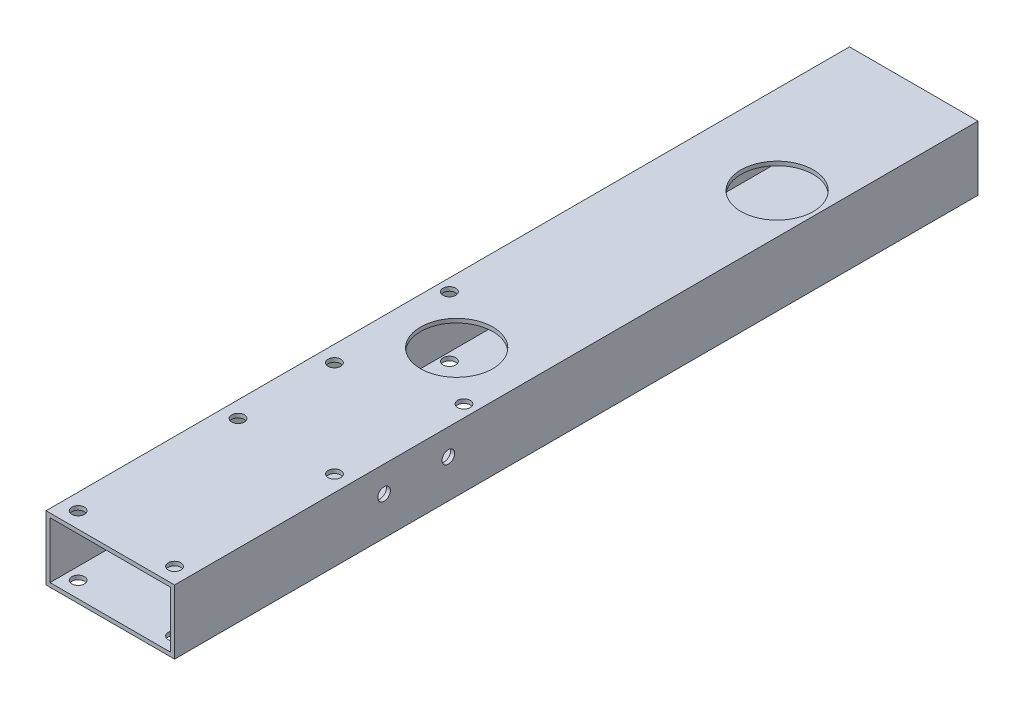
SolidWorks part; units mm, degrees
material "6061 Alloy"
ref_plane "Front Plane" through (0, 0, 0) normal (0, 0, 1) x (1, 0, 0)
ref_plane "Top Plane" through (0, 0, 0) normal (0, 1, 0) x (1, 0, 0)
ref_plane "Right Plane" through (0, 0, 0) normal (1, 0, 0) x (0, 0, -1)
sketch "Sketch1" plane through (0, 0, 0) normal (0, 0, 1) x (1, 0, 0)
  line L0 (-23.8125, 11.1125) -> (23.8125, 11.1125)
  line L2 (-25.4, 12.7) -> (25.4, 12.7)
  line L3 (-25.4, 12.7) -> (-25.4, -12.7)
  line L4 (-25.4, -12.7) -> (25.4, -12.7)
  line L5 (25.4, 12.7) -> (25.4, -12.7)
  line L10 (23.8125, 11.1125) -> (23.8125, -11.1125)
  line L11 (-23.8125, -11.1125) -> (23.8125, -11.1125)
  line L12 (-23.8125, 11.1125) -> (-23.8125, -11.1125)
  point P12 (0, 12.7)
  point P14 (25.4, 0)
  dimension "Wall Thickness" = 1.5875
  dimension "Outside Width" = 50.8
  dimension "Outside Height" = 25.4
  dimension "Inside Height" = 22.225
  dimension "Inside Width" = 47.625
sketch "Sketch2" plane through (0, 0, 0) normal (1, 0, 0) x (0, 0, -1)
  line L0 (158.75, 0) -> (-158.75, 0)
  point P4 (0, 0)
  point P7 (-158.75, 0)
  point P10 (158.75, 0)
  dimension "Length" = 317.5
sketch "Sketch3" plane through (0, 0, 0) normal (0, 0, 1) x (1, 0, 0)
  line L21 (25.4, 12.7) -> (-25.4, 12.7)
  line L22 (25.4, -12.7) -> (25.4, 12.7)
  line L23 (-25.4, -12.7) -> (25.4, -12.7)
  line L24 (-25.4, 12.7) -> (-25.4, -12.7)
  line L25 (25.4, 12.7) -> (-25.4, 12.7)
  line L26 (25.4, -12.7) -> (25.4, 12.7)
  line L27 (-25.4, -12.7) -> (25.4, -12.7)
  line L28 (-25.4, 12.7) -> (-25.4, -12.7)
  line L29 (23.8125, 11.1125) -> (-23.8125, 11.1125)
  line L30 (23.8125, -11.1125) -> (23.8125, 11.1125)
  line L31 (-23.8125, -11.1125) -> (23.8125, -11.1125)
  line L32 (-23.8125, 11.1125) -> (-23.8125, -11.1125)
  line L33 (23.8125, 11.1125) -> (-23.8125, 11.1125)
  line L34 (23.8125, -11.1125) -> (23.8125, 11.1125)
  line L35 (-23.8125, -11.1125) -> (23.8125, -11.1125)
  line L36 (-23.8125, 11.1125) -> (-23.8125, -11.1125)
  dimension "D1" = 0
  dimension "D2" = 0
extrude "Boss-Extrude1" add sketch "Sketch3" along normal up to vertex (158.75 mm away) and the other way up to vertex (158.75 mm away) up to point (0, 0, 158.75) other way up to point (0, 0, -158.75)
sketch "Drawing Reference" plane through (0, 0, 0) normal (1, 0, 0) x (0, 0, -1)
  line L0 (-158.75, 0) -> (158.75, 0) construction
  line L1 (0, -12.7) -> (0, 12.7) construction
  line L2 (-158.75, -12.7) -> (158.75, -12.7) construction
  line L5 (-158.75, 12.7) -> (158.75, 12.7) construction
  point P7 (-122.174, 0)
  point P8 (122.174, 0)
  dimension "D1" = 36.576
sketch "Sketch4" plane through (0, 12.7, 0) normal (0, 1, 0) x (1, 0, 0)
  line L0 (0, 158.75) -> (0, 95.25) construction
  line L1 (25.4, 158.75) -> (-25.4, 158.75) construction
  line L2 (0, 95.25) -> (9.525, 95.25) construction
  line L3 (0, 158.75) -> (0, -26.67) construction
  circle A1 centre (9.525, 95.25) radius 14.2875
  circle A3 centre (9.525, 95.25) radius 117.5004 construction
  circle A4 centre (0, -21.8637) radius 14.2875
  dimension "D1" = 63.5
  dimension "D3" = 235.0008
  dimension "D2" = 9.525
extrude "Cut-Extrude1" cut sketch "Sketch4" against normal blind 39.37
sketch "Sketch6" plane through (0, 12.7, 0) normal (0, 1, 0) x (1, 0, 0)
  line L0 (-20.6308, -4.1018) -> (20.6308, -39.6256) construction
  circle A0 centre (0, -21.8637) radius 27.2234 construction
  point P8 (0, -21.8637)
hole_wizard "#10 Clearance Hole1" positions "Sketch7" profile "Sketch8" hole size "#10" standard "ANSI Inch" end condition through all
sketch "Sketch7" plane through (0, 12.7, 0) normal (0, 1, 0) x (1, 0, 0)
  point P0 (-20.6308, -4.1018)
  point P3 (20.6308, -39.6256)
sketch "Sketch8" plane through (-20.6308, 12.7, 4.1018) normal (1, 0, 0) x (0, 0, 1)
  line L0 (0, 0) -> (0, 25.4)
  line L1 (0, 25.4) -> (2.4892, 25.4)
  line L2 (2.4892, 25.4) -> (2.4892, 0)
  line L5 (2.4892, 0) -> (0, 0)
  line L11 (0, -6.35) -> (0, 107.95) construction
  dimension "Thru Hole Dia." = 4.9784
  dimension "Thru Hole Depth" = 25.4
sketch "Sketch9" plane through (-25.4, 0, 0) normal (-1, 0, 0) x (0, 0, 1)
  line L0 (75.9497, 2.425) -> (50.5497, 2.425) construction
hole_wizard "#10 Clearance Hole2" positions "Sketch12" profile "Sketch13" hole size "#10" standard "ANSI Inch" end condition through all
sketch "Sketch12" plane through (-25.4, 0, 0) normal (-1, 0, 0) x (0, 0, 1)
  point P0 (50.5497, 2.425)
  point P3 (75.9497, 2.425)
sketch "Sketch13" plane through (-25.4, 2.425, 50.5497) normal (0, 1, 0) x (0, 0, 1)
  line L0 (0, 0) -> (0, 50.8)
  line L1 (0, 50.8) -> (2.4892, 50.8)
  line L2 (2.4892, 50.8) -> (2.4892, 0)
  line L5 (2.4892, 0) -> (0, 0)
  line L11 (0, -6.35) -> (0, 107.95) construction
  dimension "Thru Hole Dia." = 4.9784
  dimension "Thru Hole Depth" = 50.8
hole_wizard "#10 Clearance Hole3" positions "Sketch14" profile "Sketch15" hole size "#10" standard "ANSI Inch" end condition through all
sketch "Sketch14" plane through (0, 12.7, 0) normal (0, 1, 0) x (1, 0, 0)
  point P0 (-19.05, -51.1131)
  point P3 (-19.05, -89.2131)
  point P6 (19.05, -89.2131)
  point P9 (19.05, -152.4)
  point P12 (-19.05, -152.4)
sketch "Sketch15" plane through (-19.05, 12.7, 51.1131) normal (1, 0, 0) x (0, 0, 1)
  line L0 (0, 0) -> (0, 25.4)
  line L1 (0, 25.4) -> (2.4892, 25.4)
  line L2 (2.4892, 25.4) -> (2.4892, 0)
  line L5 (2.4892, 0) -> (0, 0)
  line L11 (0, -6.35) -> (0, 107.95) construction
  dimension "Thru Hole Dia." = 4.9784
  dimension "Thru Hole Depth" = 25.4
equation "\"D1@Drawing Reference\"=\"Outside Width@Sketch1\" * 0.72"
